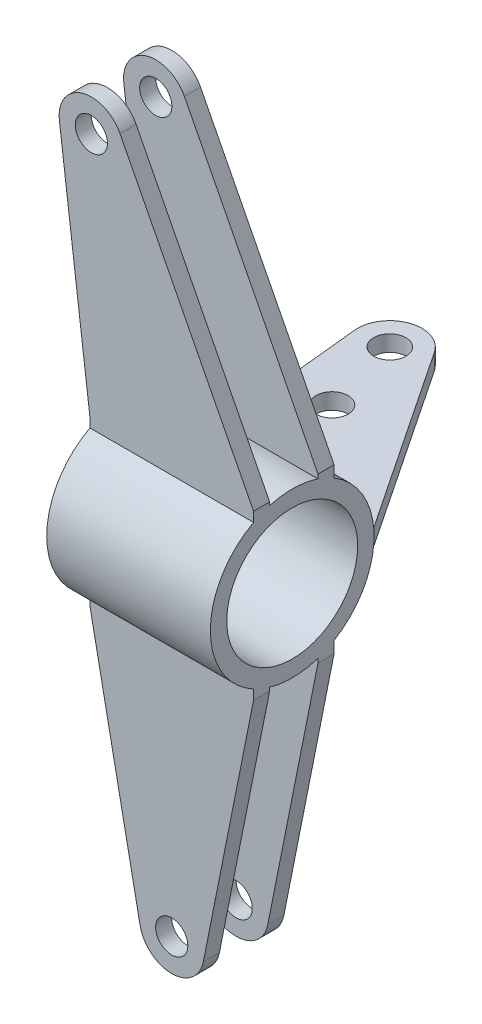
SolidWorks part; units mm, degrees
ref_plane "Front Plane" through (0, 0, 0) normal (0, 0, 1) x (1, 0, 0)
ref_plane "Top Plane" through (0, 0, 0) normal (0, 1, 0) x (1, 0, 0)
ref_plane "Right Plane" through (0, 0, 0) normal (1, 0, 0) x (0, 0, -1)
sketch "Sketch1" plane through (0, 0, 0) normal (0, 0, 1) x (1, 0, 0)
  line L0 (0, 101.6) -> (0, -101.6) construction
  line L1 (-24.9498, 101.6) -> (0, -101.6) construction
  line L2 (0, 101.6) -> (-24.9498, 101.6) construction
  point P4 (0, 0)
  dimension "D1" = 203.2
  dimension "D2" = 7
sketch "Sketch2" plane through (0, 0, 0) normal (1, 0, 0) x (0, 0, -1)
  circle A0 centre (0, 0) radius 25.4
  circle A1 centre (0, 0) radius 20.32
  dimension "D1" = 50.8
  dimension "D2" = 5.08
extrude "Boss-Extrude1" add sketch "Sketch2" along normal mid plane 50.8
sketch "Sketch3" plane through (0, 0, 0) normal (0, 0, 1) x (1, 0, 0)
  line L0 (-25.4, 25.4) -> (-34.8709, 100.3463)
  line L1 (25.4, 25.4) -> (-16.0532, 106.1662)
  line L2 (-25.4, 25.4) -> (25.4, 25.4)
  line L3 (-25.4, -25.4) -> (-9.8067, -103.5566)
  line L4 (25.4, -25.4) -> (9.8067, -103.5566)
  line L5 (-25.4, -25.4) -> (25.4, -25.4)
  circle A0 centre (-24.9498, 101.6) radius 5
  arc A1 (-16.0532, 106.1662) -> (-34.8709, 100.3463) centre (-24.9498, 101.6) ccw
  arc A2 (-9.8067, -103.5566) -> (9.8067, -103.5566) centre (0, -101.6) ccw
  circle A3 centre (0, -101.6) radius 5
  dimension "D1" = 10
  dimension "D2" = 20
  dimension "D3" = 10
  dimension "D4" = 20
extrude "Boss-Extrude2" add sketch "Sketch3" along normal blind 5 from offset 7 separate body
extrude "Boss-Extrude4" add sketch "Sketch3<3>" along normal blind 5 from offset 13 separate body offset against normal yes
sketch "Sketch3<3>" plane through (0, 0, 0) normal (0, 0, 1) x (1, 0, 0) same geometry as "Sketch3"
sketch "Sketch5" plane through (0, 0, 0) normal (1, 0, 0) x (0, 0, -1)
  line L0 (8, -25.4) -> (13, -25.4) construction
  line L1 (-12, -25.4) -> (-7, -25.4) construction
  line L2 (-12, 25.4) -> (-7, 25.4) construction
  line L3 (8, 25.4) -> (13, 25.4) construction
  line L4 (8, -25.4) -> (13, -25.4)
  line L5 (-12, -25.4) -> (-7, -25.4)
  line L6 (-12, 25.4) -> (-7, 25.4)
  line L7 (8, 25.4) -> (13, 25.4)
  line L8 (-12, 25.4) -> (-12, 22.3866)
  line L9 (-7, 25.4) -> (-7, 24.4164)
  line L10 (8, 25.4) -> (8, 24.1073)
  line L11 (13, 25.4) -> (13, 21.8211)
  line L12 (-12, -25.4) -> (-12, -22.3866)
  line L13 (-7, -25.4) -> (-7, -24.4164)
  line L14 (8, -25.4) -> (8, -24.1073)
  line L15 (13, -25.4) -> (13, -21.8211)
  circle A0 centre (0, 0) radius 25.4 construction
  arc A1 (-12, -22.3866) -> (-7, -24.4164) centre (0, 0) ccw
  arc A2 (13, 21.8211) -> (8, 24.1073) centre (0, 0) ccw
  arc A3 (-7, 24.4164) -> (-12, 22.3866) centre (0, 0) ccw
  arc A4 (8, -24.1073) -> (13, -21.8211) centre (0, 0) ccw
extrude "Boss-Extrude5" add sketch "Sketch5" along normal mid plane 50.8
sketch "Sketch6" plane through (0, 0, 0) normal (0, 1, 0) x (1, 0, 0)
  line L0 (0, 0) -> (0, 76.2) construction
  line L1 (0, 0) -> (-20.5175, 76.2) construction
  line L2 (-25.4, 25.4) -> (-30.4662, 75.1877)
  line L3 (25.4, 25.4) -> (-12.1992, 81.7503)
  line L4 (-25.4, 25.4) -> (25.4, 25.4)
  circle A0 centre (-20.5175, 76.2) radius 5
  arc A1 (-12.1992, 81.7503) -> (-30.4662, 75.1877) centre (-20.5175, 76.2) ccw
  circle A2 centre (-13.9136, 51.6735) radius 5
  dimension "D4" = 10
  dimension "D5" = 20
  dimension "D1" = 15.07
  dimension "D2" = 76.2
  dimension "D3" = 76.2
  dimension "D6" = 25.4
extrude "Boss-Extrude6" add sketch "Sketch6" along normal mid plane 5 separate body
